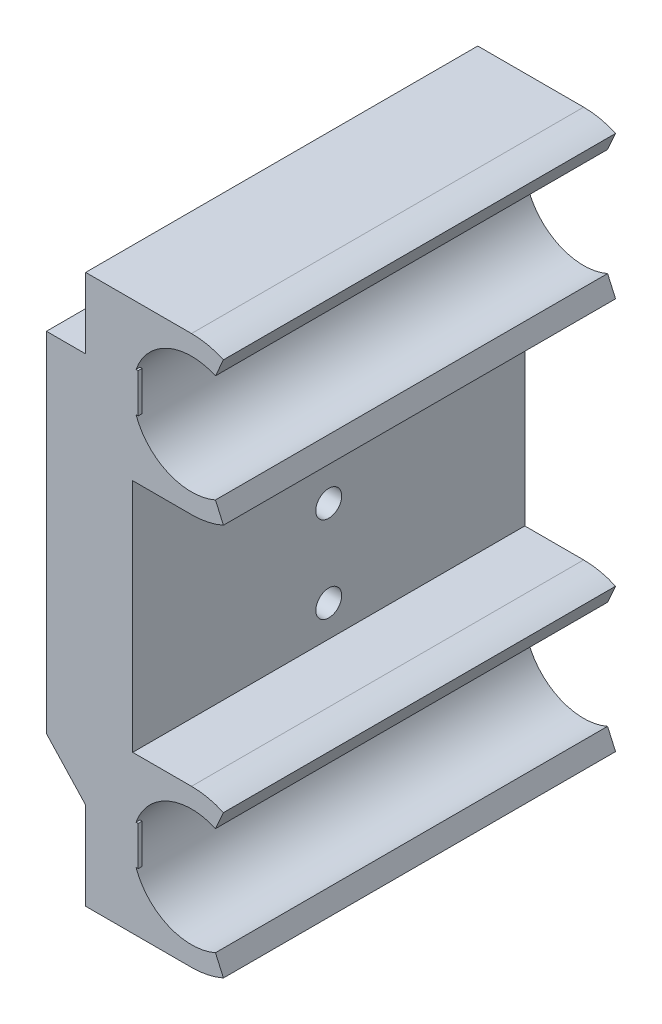
SolidWorks part; units mm, degrees
ref_plane "Plano frontal" through (0, 0, 0) normal (0, 0, 1) x (1, 0, 0)
ref_plane "Plano superior" through (0, 0, 0) normal (0, 1, 0) x (1, 0, 0)
ref_plane "Plano direito" through (0, 0, 0) normal (1, 0, 0) x (0, 0, -1)
sketch "Esboço1" plane through (0, 0, 0) normal (0, 0, 1) x (1, 0, 0)
  line L0 (0, 0) -> (67.7245, 0) construction
  line L1 (0, 35) -> (0, -35)
  line L2 (13.5, -25) -> (26.7005, -25) construction
  line L3 (16.5541, 18.15) -> (17.5721, 15.8667)
  line L4 (13.5, 15) -> (6, 15)
  line L5 (16.5541, -31.85) -> (17.5721, -34.1333)
  line L6 (6, -15) -> (6, 15)
  line L7 (13.5, -35) -> (0, -35)
  line L8 (13.5, 25) -> (26.7005, 25) construction
  line L9 (13.5, -15) -> (6, -15)
  line L10 (13.5, 35) -> (0, 35)
  line L11 (16.5541, -18.15) -> (17.5721, -15.8667)
  line L16 (16.5541, 31.85) -> (17.5721, 34.1333)
  arc A0 (16.5541, 31.85) -> (16.5541, 18.15) centre (13.5, 25) ccw
  arc A1 (17.5721, -34.1333) -> (13.5, -35) centre (13.5, -25) cw
  arc A2 (13.5, 15) -> (17.5721, 15.8667) centre (13.5, 25) ccw
  arc A3 (13.5, -15) -> (17.5721, -15.8667) centre (13.5, -25) cw
  arc A4 (16.5541, -31.85) -> (16.5541, -18.15) centre (13.5, -25) cw
  arc A5 (17.5721, 34.1333) -> (13.5, 35) centre (13.5, 25) ccw
  point P3 (0, 0)
  dimension "D1" = 15
  dimension "D2" = 13.7
  dimension "D5" = 10
  dimension "D3" = 6
  dimension "D4" = 70
extrude "Ressalto-extrusão1" add sketch "Esboço1" along normal mid plane 50
sketch "Esboço4" [suppressed] plane through (16, 0, 0) normal (1, 0, 0) x (0, 0, -1)
  line L0 (-8.5, 12.2) -> (-8.5, 15) construction
  line L1 (-23.5, 12.2) -> (-8.5, 12.2)
  line L2 (-23.5, 12.2) -> (-23.5, 18.9523)
  line L3 (-23.5, 18.9523) -> (-8.5, 18.9523)
  line L4 (-8.5, 12.2) -> (-8.5, 18.9523)
sketch "Esboço6" plane through (6, 0, 0) normal (1, 0, 0) x (0, 0, -1)
  line L0 (-25, 0) -> (25, 0) construction
  line L1 (-25, -15) -> (-25, 15) construction
  line L2 (25, -15) -> (25, 15) construction
  line L3 (0, 15) -> (0, -15) construction
  line L4 (-25, 15) -> (25, 15) construction
  line L5 (-25, -15) -> (25, -15) construction
  circle A0 centre (-20, 15) radius 1.65
  circle A1 centre (20, -15) radius 1.65
  circle A2 centre (10, -15) radius 1.65
  circle A3 centre (-10, 15) radius 1.65
  circle A4 centre (10, 15) radius 1.65
  circle A5 centre (20, 15) radius 1.65
  circle A6 centre (-10, -15) radius 1.65
  circle A7 centre (-20, -15) radius 1.65
  circle A14 centre (0, 11) radius 1.65
  circle A15 centre (0, 0) radius 1.65
  circle A16 centre (0, -11) radius 1.65
  dimension "D2" = 3.3
  dimension "D1" = 30
  dimension "D3" = 10
  dimension "D4" = 20
  dimension "D11" = 11
extrude "Corte-extrusão3" cut sketch "Esboço6" against normal blind 10 and the other way blind 6 contours A14 | A16 | A15 region at (6, 11, 0) region at (6, 0, 0) region at (6, -11, 0)
sketch "Esboço9" plane through (0, 0, 0) normal (-1, 0, 0) x (0, 0, 1)
  line L37 (3.1754, 11) -> (1.5877, 13.75)
  line L38 (1.5877, 13.75) -> (-1.5877, 13.75)
  line L39 (-1.5877, 13.75) -> (-3.1754, 11)
  line L40 (-3.1754, 11) -> (-1.5877, 8.25)
  line L41 (-1.5877, 8.25) -> (1.5877, 8.25)
  line L42 (1.5877, 8.25) -> (3.1754, 11)
  line L43 (3.1754, 0) -> (1.5877, 2.75)
  line L44 (1.5877, 2.75) -> (-1.5877, 2.75)
  line L45 (-1.5877, 2.75) -> (-3.1754, 0)
  line L46 (-3.1754, 0) -> (-1.5877, -2.75)
  line L47 (-1.5877, -2.75) -> (1.5877, -2.75)
  line L48 (1.5877, -2.75) -> (3.1754, 0)
  line L49 (3.1754, -11) -> (1.5877, -8.25)
  line L50 (1.5877, -8.25) -> (-1.5877, -8.25)
  line L51 (-1.5877, -8.25) -> (-3.1754, -11)
  line L52 (-3.1754, -11) -> (-1.5877, -13.75)
  line L53 (-1.5877, -13.75) -> (1.5877, -13.75)
  line L54 (1.5877, -13.75) -> (3.1754, -11)
  circle A6 centre (0, 11) radius 2.75 construction
  circle A7 centre (0, 0) radius 2.75 construction
  circle A8 centre (0, -11) radius 2.75 construction
  dimension "D1" = 5.5
extrude "Corte-extrusão5" cut sketch "Esboço9" against normal blind 3
sketch "Esboço10" plane through (0, 0, 0) normal (-1, 0, 0) x (0, 0, 1)
  line L0 (-25, 32.5) -> (-25, 17.5) construction
  line L1 (-25, 27.5) -> (-24.5, 27.5)
  line L2 (-25, 27.5) -> (-25, 22.5)
  line L3 (-25, 22.5) -> (-24.5, 22.5)
  line L4 (-24.5, 27.5) -> (-24.5, 22.5)
  line L5 (25, 25) -> (-33.7346, 25) construction
  line L6 (25, 17.5) -> (25, 32.5) construction
  line L7 (25, 0) -> (0, 0) construction
  line L8 (25, -15) -> (25, 15) construction
  line L9 (0, 0) -> (0, 35.3595) construction
  line L10 (24.5, 27.5) -> (24.5, 22.5)
  line L11 (25, 22.5) -> (24.5, 22.5)
  line L12 (25, 27.5) -> (25, 22.5)
  line L13 (25, 27.5) -> (24.5, 27.5)
  line L14 (25, -27.5) -> (24.5, -27.5)
  line L15 (25, -27.5) -> (25, -22.5)
  line L16 (25, -22.5) -> (24.5, -22.5)
  line L17 (24.5, -27.5) -> (24.5, -22.5)
  line L18 (-24.5, -27.5) -> (-24.5, -22.5)
  line L19 (-25, -22.5) -> (-24.5, -22.5)
  line L20 (-25, -27.5) -> (-25, -22.5)
  line L21 (-25, -27.5) -> (-24.5, -27.5)
  point P15 (-24.5, 25)
  dimension "D1" = 5
  dimension "D2" = 0.5
extrude "Ressalto-extrusão3" add sketch "Esboço10" against normal blind 6.7
sketch "Esboço11" plane through (0, 0, 0) normal (-1, 0, 0) x (0, 0, 1)
  line L0 (-17.5, -7) -> (0, -14)
  line L1 (25, 35) -> (-25, 35) construction
  line L2 (-17.5, 26) -> (-17.5, -7)
  line L4 (17.5, 26) -> (17.5, -7)
  line L5 (-17.5, 26) -> (17.5, -7) construction
  line L6 (-17.5, -7) -> (17.5, 26) construction
  line L7 (0, -14) -> (17.5, -7)
  line L9 (-25, 26) -> (-17.5, 26)
  line L10 (25, 26) -> (25, -16.9244)
  line L11 (25, 35) -> (25, -35) construction
  line L12 (25, -16.9244) -> (0, -26.9244)
  line L13 (0, -26.9244) -> (-25, -16.9244)
  line L14 (-25, 35) -> (-25, -35) construction
  line L15 (-25, -16.9244) -> (-25, 26)
  line L17 (17.5, 26) -> (25, 26)
  point P0 (0, 9.5)
  dimension "D1" = 35
  dimension "D2" = 7
  dimension "D3" = 42
  dimension "D4" = 33
  dimension "D5" = 12
extrude "Ressalto-extrusão4" add sketch "Esboço11" along normal blind 5
sketch "Esboço12" plane through (-5, 0, 0) normal (-1, 0, 0) x (0, 0, 1)
  line L0 (-17.5, -7) -> (17.5, -7)
  line L1 (17.5, -7) -> (17.5, -14)
  line L2 (17.5, -14) -> (0, -21)
  line L3 (0, -21) -> (-17.5, -14)
  line L4 (-17.5, -14) -> (-17.5, -7)
  line L5 (-17.5, -7) -> (-1.8768, -13.2493) construction
  dimension "D1" = 7
extrude "Corte-extrusão6" cut sketch "Esboço12" against normal up to surface (5 mm away) from offset 1 up to face at (0, 11, 0) offset against normal yes
chamfer "Chanfro1" distance 6.4 angle 45 2 edges at (-4, -17.5, -8.75) (-4, -17.5, 8.75)
sketch "Esboço13" plane through (0, 0, 0) normal (-1, 0, 0) x (0, 0, 1)
  circle A0 centre (0, 30.5) radius 1.65
  point P4 (17.5, -7)
  dimension "D1" = 37.5
  dimension "D2" = 3.3
extrude "Corte-extrusão7" cut sketch "Esboço13" against normal blind 13
sketch "Esboço14" plane through (0, 0, 0) normal (-1, 0, 0) x (0, 0, 1)
  line L1 (3.1754, 30.5) -> (1.5877, 33.25)
  line L2 (1.5877, 33.25) -> (-1.5877, 33.25)
  line L3 (-1.5877, 33.25) -> (-3.1754, 30.5)
  line L4 (-3.1754, 30.5) -> (-1.5877, 27.75)
  line L5 (-1.5877, 27.75) -> (1.5877, 27.75)
  line L6 (1.5877, 27.75) -> (3.1754, 30.5)
  circle A0 centre (0, 30.5) radius 2.75 construction
  dimension "D1" = 5.5
extrude "Corte-extrusão8" cut sketch "Esboço14" against normal blind 10 from offset 4 offset against normal yes
chamfer "Chanfro2" distance 6.4 angle 45 2 edges at (0, -21.9244, -12.5) (0, -21.9244, 12.5)
